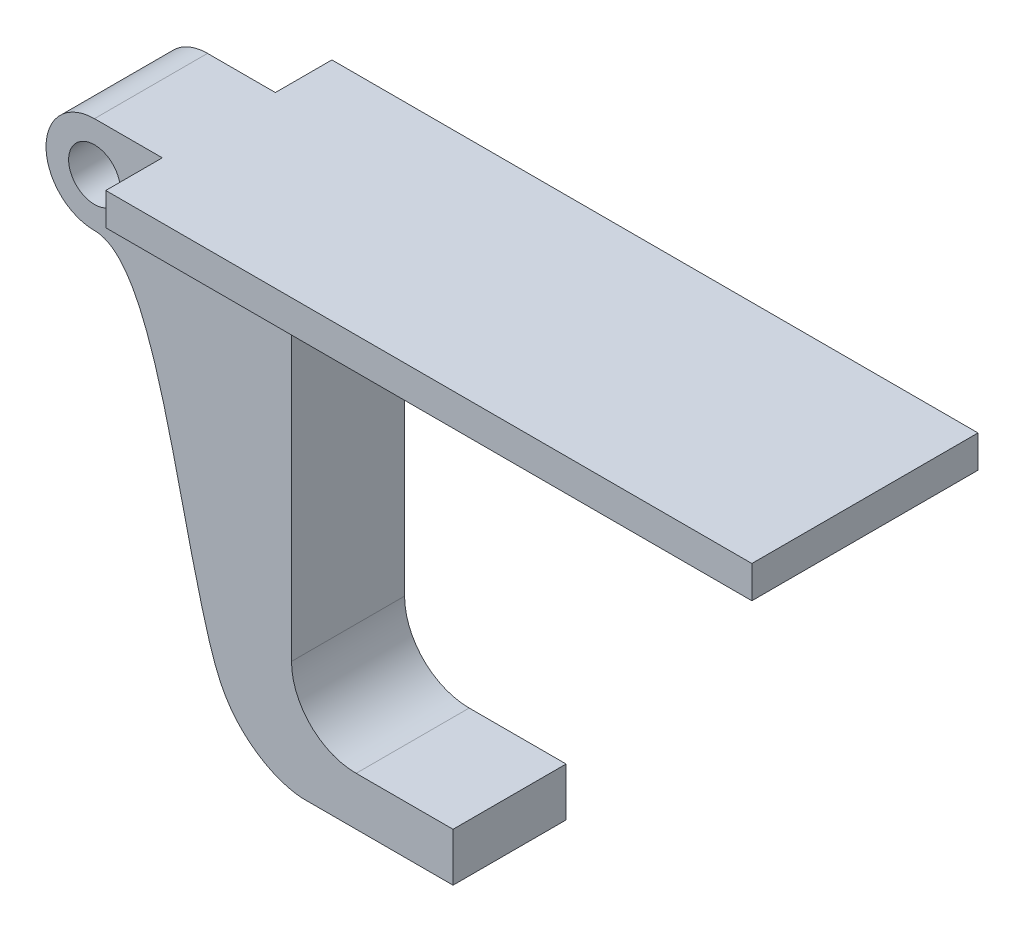
SolidWorks part; units mm, degrees
ref_plane "Ebene vorne" through (0, 0, 0) normal (0, 0, 1) x (1, 0, 0)
ref_plane "Ebene oben" through (0, 0, 0) normal (0, 1, 0) x (1, 0, 0)
ref_plane "Ebene rechts" through (0, 0, 0) normal (1, 0, 0) x (0, 0, -1)
sketch "Sketch1" plane through (0, 0, 0) normal (0, 1, 0) x (1, 0, 0)
  line L0 (-20, -7) -> (-20, -3.5)
  line L1 (-20, -7) -> (20, -7)
  line L2 (-20, 7) -> (20, 7)
  line L3 (20, -7) -> (20, 7)
  line L4 (-20, -7) -> (20, 7) construction
  line L5 (-20, 7) -> (20, -7) construction
  line L6 (-20, 3.5) -> (-20, 7)
  line L7 (-20, -3.5) -> (-27.2, -3.5)
  line L9 (-20, 3.5) -> (-27.2, 3.5)
  line L10 (-27.2, -3.5) -> (-27.2, 3.5)
  point P1 (0, 0)
  dimension "D1" = 14
  dimension "D2" = 40
  dimension "D3" = 7.2
  dimension "D4" = 7
extrude "Boss-Extrude1" add sketch "Sketch1" along normal blind 2
sketch "Sketch16" plane through (0, 0, 0) normal (0, -1, 0) x (1, 0, 0)
  line L1 (-20, 3.5) -> (-27.2, 3.5)
  line L2 (-20, 3.5) -> (-20, -3.5)
  line L3 (-20, -3.5) -> (-27.2, -3.5)
  line L4 (-27.2, 3.5) -> (-27.2, -3.5)
extrude "Boss-Extrude3" add sketch "Sketch16" along normal blind 4
sketch "Sketch17" plane through (0, 0, -3.5) normal (0, 0, -1) x (-1, 0, 0)
  line L0 (20, 2) -> (27.2, 2) construction
  line L1 (27.2, 2) -> (27.2, -4) construction
  circle A0 centre (24.2, -1) radius 1.6
  dimension "D1" = 3.2
  dimension "D2" = 3
  dimension "D3" = 3
extrude "Cut-Extrude4" cut sketch "Sketch17" against normal up to next
fillet "Fillet4" radius 3 2 edges at (-27.2, -4, 0) (-27.2, 2, 0)
sketch "Sketch18" plane through (0, 0, -3.5) normal (0, 0, -1) x (-1, 0, 0)
  line L1 (12, -21) -> (12, 0)
  line L2 (-20, 0) -> (20, 0) construction
  line L3 (12, 0) -> (20, 0)
  line L5 (2, -28) -> (10.9538, -28)
  line L6 (2, -28) -> (2, -25)
  line L7 (2, -25) -> (8, -25)
  line L10 (26.8692, -4) -> (21.5308, -4) construction
  line L11 (20, 0) -> (20, -4)
  line L12 (20, -4) -> (24.2, -4)
  arc A0 (8, -25) -> (12, -21) centre (8, -21) ccw
  spline S0 degree 3 poles (10.9538, -28) (12.5005, -28.089) (15.746, -26.6307) (19.1654, -16.2215) (20.6164, -4) (24.2, -4) knots 0 0 0 0 0.247683 0.347683 1 1 1 1
  point P8 (16.4681, -24.1644)
  point P15 (12, -25)
  dimension "D3" = 4
  dimension "D1" = 25
  dimension "D2" = 3
  dimension "D4" = 10
  dimension "D5" = 8
extrude "Boss-Extrude4" add sketch "Sketch18" against normal up to surface (7 mm away) up to face at (-25.8, -1, 3.5)
sketch "Sketch15" plane through (0, 0, 0) normal (0, -1, 0) x (1, 0, 0)
  line L0 (1, 0) -> (3, 0) construction
  line L1 (1, 3.5) -> (3, 3.5)
  line L2 (1, -3.5) -> (3, -3.5)
  line L7 (-2, 3.5) -> (-10.9538, 3.5)
  line L8 (-10.9538, 3.5) -> (-10.9538, -3.5)
  line L9 (-10.9538, -3.5) -> (-2, -3.5)
  line L10 (-2, -3.5) -> (-2, 3.5)
  line L11 (-2, 3.5) -> (-10.9538, 3.5) construction
  line L12 (-10.9538, 3.5) -> (-10.9538, -3.5) construction
  line L13 (-10.9538, -3.5) -> (-2, -3.5) construction
  line L14 (-2, -3.5) -> (-2, 3.5) construction
  arc A0 (1, 3.5) -> (1, -3.5) centre (1, 0) ccw
  arc A1 (3, -3.5) -> (3, 3.5) centre (3, 0) ccw
  point P3 (2, 0)
  dimension "D1" = 7
  dimension "D2" = 2
  dimension "D3" = 0
  dimension "D4" = 4
extrude "Cut-Extrude3" [suppressed] cut sketch "Sketch15" against normal up to next
